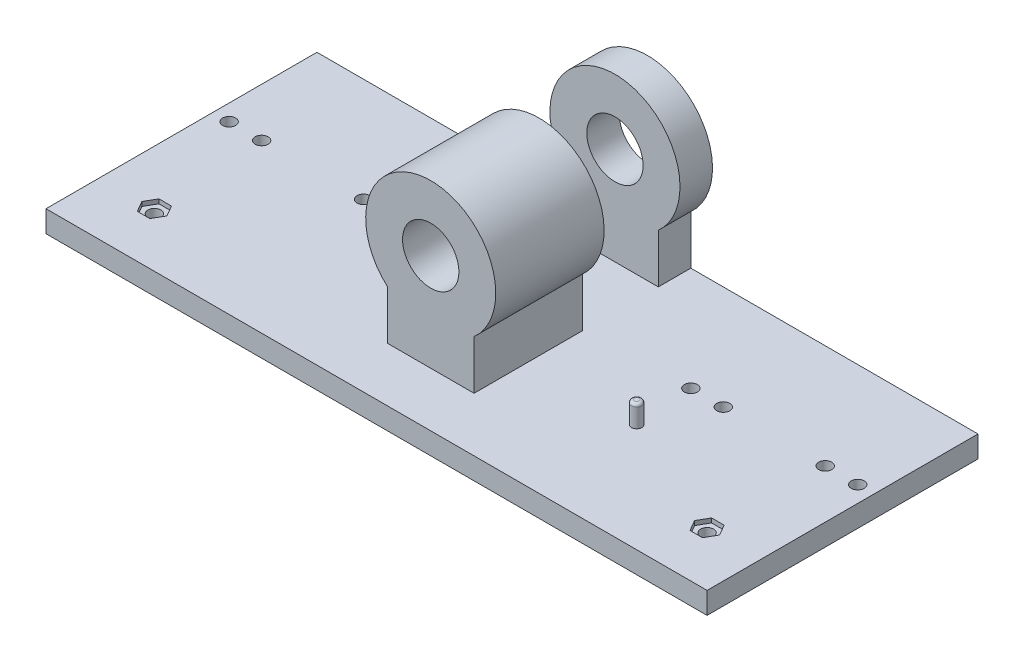
SolidWorks part; units mm, degrees
ref_plane "Front Plane" through (0, 0, 0) normal (0, 0, 1) x (1, 0, 0)
ref_plane "Top Plane" through (0, 0, 0) normal (0, 1, 0) x (1, 0, 0)
ref_plane "Right Plane" through (0, 0, 0) normal (1, 0, 0) x (0, 0, -1)
sketch "Sketch1" plane through (0, 0, 0) normal (0, 1, 0) x (1, 0, 0)
  line L0 (152.5, 125) -> (152.5, 0) construction
  line L1 (0, 0) -> (305, 0)
  line L2 (0, 0) -> (0, 125)
  line L3 (0, 125) -> (305, 125)
  line L4 (305, 0) -> (305, 125)
  line L5 (25, 100) -> (280, 100) construction
  line L6 (280, 25) -> (280, 100) construction
  line L7 (25, 25) -> (280, 25) construction
  line L8 (25, 25) -> (25, 100) construction
  line L9 (152.5, 62.5) -> (25, 62.5) construction
  line L10 (30.7735, 100) -> (27.8868, 105) construction
  line L11 (27.8868, 105) -> (22.1132, 105) construction
  line L12 (22.1132, 105) -> (19.2265, 100) construction
  line L13 (19.2265, 100) -> (22.1132, 95) construction
  line L14 (22.1132, 95) -> (27.8868, 95) construction
  line L15 (27.8868, 95) -> (30.7735, 100) construction
  line L16 (27.8868, 30) -> (30.7735, 25) construction
  line L17 (22.1132, 30) -> (27.8868, 30) construction
  line L18 (19.2265, 25) -> (22.1132, 30) construction
  line L19 (22.1132, 20) -> (19.2265, 25) construction
  line L20 (27.8868, 20) -> (22.1132, 20) construction
  line L21 (30.7735, 25) -> (27.8868, 20) construction
  line L22 (282.8868, 30) -> (277.1132, 30) construction
  line L23 (285.7735, 25) -> (282.8868, 30) construction
  line L24 (282.8868, 20) -> (285.7735, 25) construction
  line L25 (277.1132, 20) -> (282.8868, 20) construction
  line L26 (274.2265, 25) -> (277.1132, 20) construction
  line L27 (277.1132, 30) -> (274.2265, 25) construction
  line L28 (277.1132, 95) -> (274.2265, 100) construction
  line L29 (282.8868, 95) -> (277.1132, 95) construction
  line L30 (285.7735, 100) -> (282.8868, 95) construction
  line L31 (282.8868, 105) -> (285.7735, 100) construction
  line L32 (277.1132, 105) -> (282.8868, 105) construction
  line L33 (274.2265, 100) -> (277.1132, 105) construction
  line L34 (172.5, 75) -> (172.5, 125) construction
  line L35 (132.5, 0) -> (172.5, 0) construction
  line L36 (132.5, 0) -> (132.5, 125) construction
  line L37 (132.5, 125) -> (172.5, 125) construction
  line L38 (172.5, 0) -> (172.5, 125) construction
  line L39 (132.5, 75) -> (172.5, 75) construction
  line L40 (132.5, 75) -> (132.5, 25) construction
  line L41 (132.5, 25) -> (172.5, 25) construction
  line L42 (172.5, 75) -> (172.5, 25) construction
  line L50 (132.5, 75) -> (117.5, 75) construction
  line L51 (0, 84.5) -> (15, 69.5) construction
  line L52 (132.5, 75) -> (117.5, 62.5) construction
  line L53 (117.5, 62.5) -> (117.5, 87.5) construction
  line L54 (0, 125) -> (108, 125) construction
  line L55 (0, 125) -> (0, 84.5) construction
  line L56 (0, 84.5) -> (108, 84.5) construction
  line L57 (108, 125) -> (108, 84.5) construction
  line L58 (15, 69.5) -> (15, 84.5) construction
  line L59 (30, 84.5) -> (0, 84.5) construction
  line L60 (30, 84.5) -> (30, 69.5) construction
  line L61 (30, 69.5) -> (0, 69.5) construction
  line L62 (0, 84.5) -> (0, 69.5) construction
  line L63 (92, 84.5) -> (92, 69.5) construction
  line L64 (62, 0) -> (62, 125) construction
  circle A1 centre (25, 100) radius 5 construction
  circle A3 centre (280, 25) radius 3
  circle A4 centre (25, 25) radius 3
  circle A8 centre (117.5, 62.5) radius 3
  circle A9 centre (117.5, 87.5) radius 3
  circle A10 centre (7.5, 77) radius 3
  circle A11 centre (22.5, 77) radius 3
  circle A12 centre (69.5, 77) radius 3
  circle A13 centre (84.5, 77) radius 3
  circle A14 centre (220.5, 77) radius 3
  circle A15 centre (235.5, 77) radius 3
  circle A16 centre (282.5, 77) radius 3
  circle A17 centre (297.5, 77) radius 3
  dimension "D3" = 6
  dimension "D1" = 305
  dimension "D2" = 125
  dimension "D5" = 10
  dimension "D6" = 40
  dimension "D8" = 50
  dimension "D12" = 15
  dimension "D7" = 40.5
  dimension "D9" = 108
  dimension "D10" = 15
  dimension "D11" = 30
  dimension "D15" = 62
  dimension "D4" = 25
  dimension "D13" = 2
  dimension "D14" = 2
extrude "Boss-Extrude1" add sketch "Sketch1" along normal blind 10
sketch "Sketch6" plane through (0, 10, 0) normal (0, 1, 0) x (1, 0, 0)
  line L0 (152.5, 125) -> (152.5, 0) construction
  line L7 (305, 125) -> (0, 125) construction
  line L8 (0, 0) -> (305, 0) construction
  line L9 (152.5, 62.5) -> (0, 62.5) construction
  line L10 (0, 125) -> (0, 0) construction
  line L29 (27.8868, 30) -> (30.7735, 25)
  line L30 (274.2265, 25) -> (277.1132, 20)
  line L31 (277.1132, 20) -> (282.8868, 20)
  line L32 (282.8868, 20) -> (285.7735, 25)
  line L33 (285.7735, 25) -> (282.8868, 30)
  line L34 (282.8868, 30) -> (277.1132, 30)
  line L35 (277.1132, 30) -> (274.2265, 25)
  line L36 (22.1132, 30) -> (27.8868, 30)
  line L37 (19.2265, 25) -> (22.1132, 30)
  line L38 (22.1132, 20) -> (19.2265, 25)
  line L39 (27.8868, 20) -> (22.1132, 20)
  line L40 (30.7735, 25) -> (27.8868, 20)
  circle A0 centre (280, 25) radius 5 construction
  dimension "D1" = 10
extrude "Cut-Extrude1" cut sketch "Sketch6" against normal blind 2
sketch "Sketch7" plane through (0, 10, 0) normal (0, 1, 0) x (1, 0, 0)
  line L0 (0, 0) -> (305, 0) construction
  line L1 (132.5, 25) -> (172.5, 25)
  line L2 (132.5, 25) -> (132.5, 75)
  line L3 (132.5, 75) -> (172.5, 75)
  line L4 (172.5, 25) -> (172.5, 75)
  line L5 (152.5, 0) -> (152.5, 125) construction
  line L6 (305, 125) -> (0, 125) construction
  line L7 (172.5, 75) -> (172.5, 125) construction
  line L18 (132.5, 110) -> (172.5, 110)
  line L19 (132.5, 110) -> (132.5, 125)
  line L20 (132.5, 125) -> (172.5, 125)
  line L21 (172.5, 110) -> (172.5, 125)
  point P11 (152.5, 75)
  point P20 (152.5, 110)
  dimension "D1" = 40
  dimension "D2" = 50
  dimension "D4" = 15
extrude "Boss-Extrude2" add sketch "Sketch7" along normal blind 22.6393
sketch "Sketch11" plane through (0, 0, -25) normal (0, 0, 1) x (1, 0, 0)
  circle A0 centre (152.5, 55) radius 30
  circle A1 centre (152.5, 55) radius 13
  dimension "D1" = 60
  dimension "D2" = 26
extrude "Boss-Extrude3" add sketch "Sketch11" against normal up to surface (100 mm away) up to face at (152.5, 13.1598, -125)
ref_plane "Plane1" through (0, 0, -62.5) normal (0, 0, 1) x (1, 0, 0)
sketch "Sketch12" plane through (305, 0, 0) normal (1, 0, 0) x (0, 0, -1)
  line L0 (125, 85) -> (25, 85) construction
  line L1 (75, 10) -> (110, 10)
  line L2 (75, 10) -> (75, 85)
  line L3 (75, 85) -> (110, 85)
  line L4 (110, 10) -> (110, 85)
  line L6 (110, 32.6393) -> (110, 10) construction
extrude "Cut-Extrude2" cut sketch "Sketch12" against normal through all
sketch "Sketch13" plane through (0, 10, 0) normal (0, 1, 0) x (1, 0, 0)
  line L0 (222.5, 50) -> (172.5, 50) construction
  line L1 (172.5, 25) -> (172.5, 75) construction
  circle A1 centre (222.5, 50) radius 2.4
  dimension "D1" = 4.8
  dimension "D2" = 50
extrude "Boss-Extrude4" add sketch "Sketch13" along normal blind 10
sketch "Sketch14" plane through (0, 0, 0) normal (0, -1, 0) x (1, 0, 0)
  line L12 (123.2735, -87.5) -> (120.3868, -82.5)
  line L13 (123.2735, -62.5) -> (120.3868, -57.5)
  line L14 (120.3868, -57.5) -> (114.6132, -57.5)
  line L15 (114.6132, -57.5) -> (111.7265, -62.5)
  line L16 (111.7265, -62.5) -> (114.6132, -67.5)
  line L17 (114.6132, -67.5) -> (120.3868, -67.5)
  line L18 (120.3868, -67.5) -> (123.2735, -62.5)
  line L19 (120.3868, -82.5) -> (114.6132, -82.5)
  line L20 (114.6132, -82.5) -> (111.7265, -87.5)
  line L21 (111.7265, -87.5) -> (114.6132, -92.5)
  line L22 (114.6132, -92.5) -> (120.3868, -92.5)
  line L23 (120.3868, -92.5) -> (123.2735, -87.5)
  circle A0 centre (117.5, -62.5) radius 5 construction
  dimension "D1" = 10
  dimension "D3" = 15
  dimension "D2" = 2
fillet "Fillet1" radius 1.3 1 edges at (222.5, 20, -47.6)
extrude "Cut-Extrude3" cut sketch "Sketch14" against normal blind 4
equation "\"joint_width\"=4"
equation "\"D2@Sketch7\"=5"
equation "\"short_base_length\"=12.5"
equation "\"D2@Sketch1\"=\"short_base_length\""
equation "\"outer_diam_main_joint\"=6"
equation "\"D1@Sketch11\"=\"outer_diam_main_joint\""
equation "\"D1@Sketch7\"=\"outer_diam_main_joint\"-2"
equation "\"D1@Boss-Extrude2\"=(\"outer_diam_main_joint\"/2)+1.5cm-sqr((\"outer_diam_main_joint\"/2)^2-((\"outer_diam_main_joint\"-2)/2)^2)"
equation "\"D6@Sketch1\"=\"outer_diam_main_joint\"-2"
equation "\"pulleyside\"=1.5"
